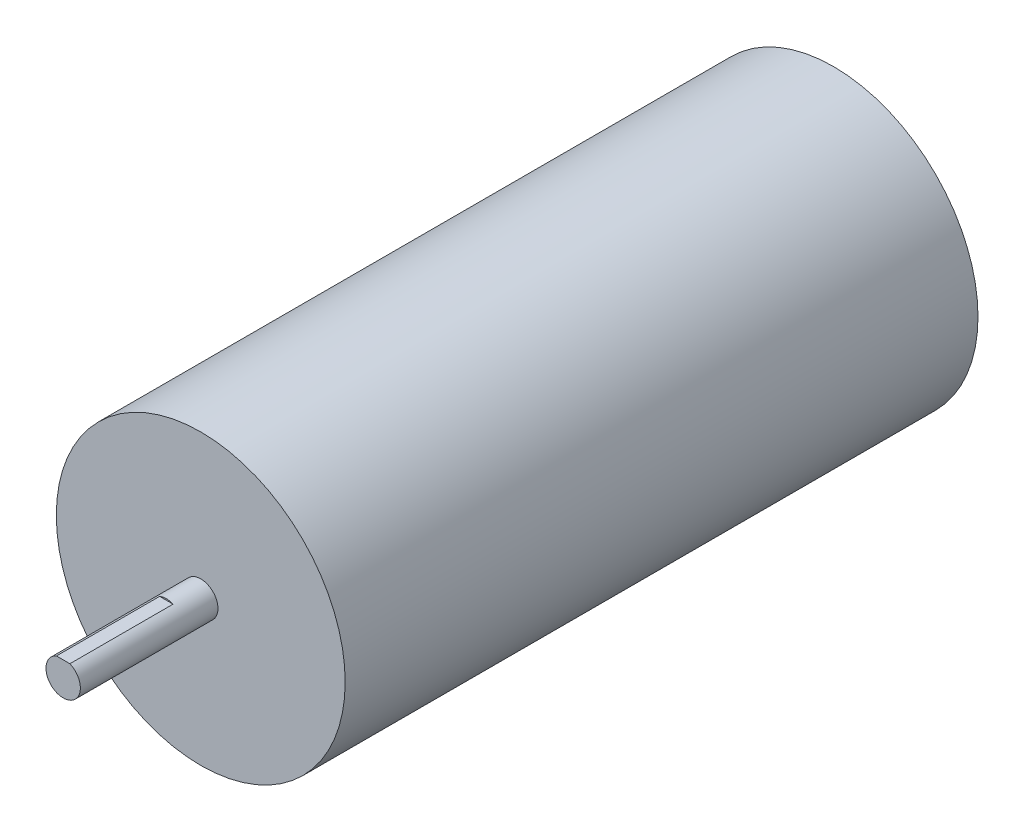
SolidWorks part; units mm, degrees
ref_plane "Plano frontal" through (0, 0, 0) normal (0, 0, 1) x (1, 0, 0)
ref_plane "Plano superior" through (0, 0, 0) normal (0, 1, 0) x (1, 0, 0)
ref_plane "Plano direito" through (0, 0, 0) normal (1, 0, 0) x (0, 0, -1)
sketch "Esboço1" plane through (0, 0, 0) normal (0, 0, 1) x (1, 0, 0)
  circle A0 centre (0, 0) radius 21
  dimension "D1" = 42
extrude "Ressalto-extrusão1" add sketch "Esboço1" along normal blind 92
sketch "Esboço2" plane through (0, 0, 92) normal (0, 0, 1) x (1, 0, 0)
  circle A0 centre (0, 0) radius 2.5
  dimension "D1" = 5
extrude "Ressalto-extrusão2" add sketch "Esboço2" along normal blind 20
sketch "Esboço3" plane through (0, 0, 112) normal (0, 0, 1) x (1, 0, 0)
  line L0 (-0.9798, 2.3) -> (0.9798, 2.3)
  circle A0 centre (0, 0) radius 2.5 construction
  arc A1 (-0.9798, 2.3) -> (0.9798, 2.3) centre (0, 0) cw
  point P7 (0, 2.5)
  dimension "D1" = 0.2
extrude "Corte-extrusão1" cut sketch "Esboço3" against normal blind 15
